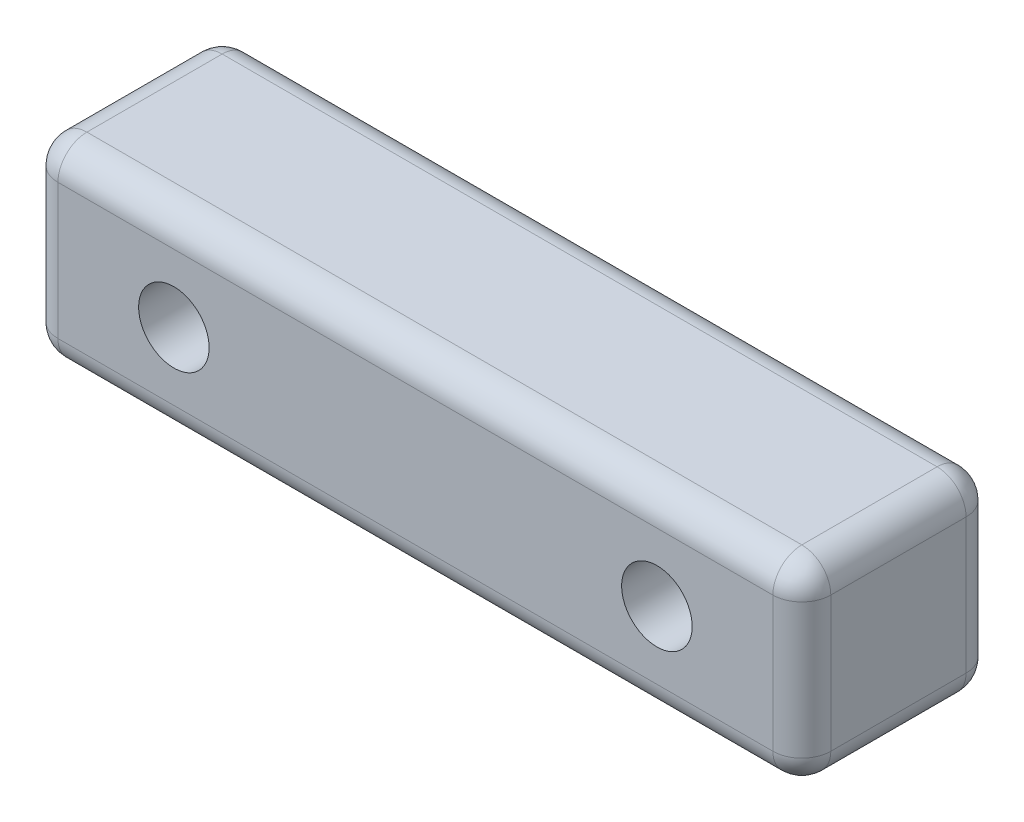
SolidWorks part; units mm, degrees
ref_plane "Alzado" through (0, 0, 0) normal (0, 0, 1) x (1, 0, 0)
ref_plane "Planta" through (0, 0, 0) normal (0, 1, 0) x (1, 0, 0)
ref_plane "Vista lateral" through (0, 0, 0) normal (1, 0, 0) x (0, 0, -1)
sketch "Croquis1" plane through (0, 0, 0) normal (0, 0, 1) x (1, 0, 0)
  line L0 (40, 0) -> (-40, 0) construction
  line L1 (-40, 10) -> (40, 10)
  line L2 (40, 10) -> (40, -10)
  line L3 (40, -10) -> (-40, -10)
  line L4 (-40, -10) -> (-40, 10)
  line L5 (0, 0) -> (0, -3.7626) construction
  circle A0 centre (25, 0) radius 3.65
  circle A1 centre (-25, 0) radius 3.65
  point P4 (0, 0)
  point P7 (-40, 0)
  dimension "D4" = 7.3
  dimension "D1" = 80
  dimension "D2" = 20
  dimension "D3" = 15
extrude "Saliente-Extruir1" add sketch "Croquis1" along normal blind 20
sketch "Croquis2" plane through (0, 0, 20) normal (0, 0, 1) x (1, 0, 0)
  line L0 (0, 0) -> (0, 5.7256) construction
  line L7 (20, -10) -> (40, -10)
  line L8 (20, 10) -> (20, -10)
  line L9 (40, 10) -> (20, 10)
  line L10 (40, -10) -> (40, 10)
  dimension "D1" = 20
extrude "Cortar-Extruir1" [suppressed] cut sketch "Croquis2" against normal blind 10
sketch "Croquis3" plane through (0, 0, 0) normal (0, 0, -1) x (-1, 0, 0)
  line L0 (40, 10) -> (20, 10)
  line L1 (-40, 10) -> (40, 10) construction
  line L2 (20, 10) -> (20, -10)
  line L3 (40, -10) -> (-40, -10) construction
  line L4 (20, -10) -> (40, -10)
  line L5 (40, -10) -> (40, 10)
  line L6 (-20, 10) -> (-20, -10)
  line L7 (-20, -10) -> (-40, -10)
  line L8 (-40, -10) -> (-40, 10)
  line L9 (-40, 10) -> (-20, 10)
  dimension "D1" = 20
  dimension "D2" = 20
extrude "Cortar-Extruir2" [suppressed] cut sketch "Croquis3" against normal blind 10
fillet "Redondeo1" radius 3 12 edges at (0, -10, 20) (-40, -10, 10) (-40, 0, 20) (0, 10, 20) (40, 0, 20) (40, -10, 10) (0, -10, 0) (-40, 0, 0) (-40, 10, 10) (40, 10, 10) (40, 0, 0) (0, 10, 0)
